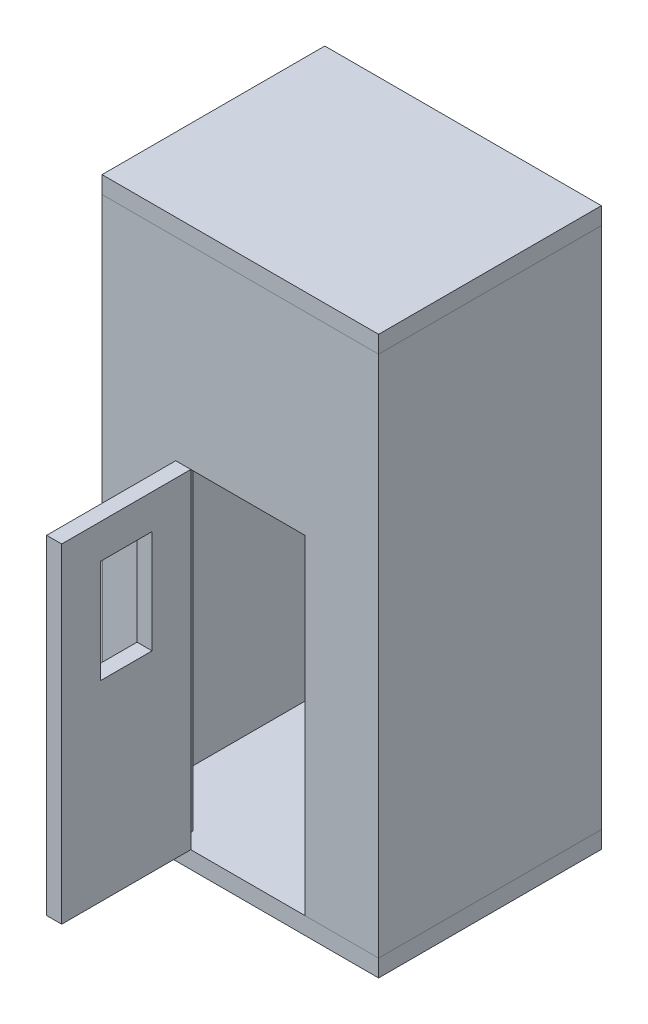
SolidWorks part; units mm, degrees
ref_plane "Front" through (0, 0, 0) normal (0, 0, 1) x (1, 0, 0)
ref_plane "Top" through (0, 0, 0) normal (0, 1, 0) x (1, 0, 0)
ref_plane "Right" through (0, 0, 0) normal (1, 0, 0) x (0, 0, -1)
sketch "Sketch1" plane through (0, 0, 0) normal (0, 1, 0) x (1, 0, 0)
  line L0 (-714.375, 555.625) -> (714.375, 555.625)
  line L1 (-815.975, -657.225) -> (815.975, -657.225)
  line L2 (-815.975, -657.225) -> (-815.975, 657.225)
  line L3 (-815.975, 657.225) -> (815.975, 657.225)
  line L4 (815.975, -657.225) -> (815.975, 657.225)
  line L5 (-815.975, -657.225) -> (815.975, 657.225) construction
  line L6 (-815.975, 657.225) -> (815.975, -657.225) construction
  line L7 (714.375, -555.625) -> (714.375, 555.625)
  line L8 (-714.375, -555.625) -> (714.375, -555.625)
  line L9 (-714.375, -555.625) -> (-714.375, 555.625)
  point P0 (0, 0)
  dimension "D1" = 1314.45
  dimension "D2" = 1631.95
  dimension "D3" = 101.6
extrude "Boss-Extrude1" add sketch "Sketch1" along normal blind 3086.1
sketch "Sketch2" plane through (0, 3086.1, 0) normal (0, 1, 0) x (1, 0, 0)
  line L4 (815.975, -657.225) -> (815.975, 657.225)
  line L5 (815.975, 657.225) -> (-815.975, 657.225)
  line L6 (-815.975, 657.225) -> (-815.975, -657.225)
  line L7 (-815.975, -657.225) -> (815.975, -657.225)
  line L8 (815.975, -657.225) -> (815.975, 657.225)
  line L9 (815.975, 657.225) -> (-815.975, 657.225)
  line L10 (-815.975, 657.225) -> (-815.975, -657.225)
  line L11 (-815.975, -657.225) -> (815.975, -657.225)
  dimension "D1" = 0
extrude "Boss-Extrude2" add sketch "Sketch2" along normal blind 101.6 separate body
sketch "Sketch3" plane through (0, 0, 657.225) normal (0, 0, 1) x (1, 0, 0)
  line L0 (-815.975, 0) -> (815.975, 0) construction
  line L1 (-381, 0) -> (381, 0)
  line L2 (-381, 0) -> (-381, 1943.1)
  line L3 (-381, 1943.1) -> (381, 1943.1)
  line L4 (381, 0) -> (381, 1943.1)
  line L5 (0, 1943.1) -> (0, 0) construction
  dimension "D1" = 1943.1
  dimension "D2" = 762
extrude "Cut-Extrude1" cut sketch "Sketch3" against normal up to next (101.6 mm away)
sketch "Sketch4" plane through (0, 0, 0) normal (0, -1, 0) x (1, 0, 0)
  line L1 (-815.975, -657.225) -> (815.975, -657.225)
  line L2 (-815.975, -657.225) -> (-815.975, 657.225)
  line L3 (-815.975, 657.225) -> (815.975, 657.225)
  line L4 (815.975, -657.225) -> (815.975, 657.225)
  line L5 (-815.975, -657.225) -> (815.975, 657.225) construction
  line L6 (-815.975, 657.225) -> (815.975, -657.225) construction
  point P0 (0, 0)
extrude "Boss-Extrude3" add sketch "Sketch4" along normal blind 101.6 separate body
sketch "Sketch5" plane through (0, 0, -555.625) normal (0, 0, 1) x (1, 0, 0)
  line L4 (-714.375, 0) -> (714.375, 0)
  line L5 (714.375, 0) -> (714.375, 3086.1)
  line L6 (714.375, 3086.1) -> (-714.375, 3086.1)
  line L7 (-714.375, 3086.1) -> (-714.375, 0)
  line L8 (-714.375, 0) -> (714.375, 0)
  line L9 (714.375, 0) -> (714.375, 3086.1)
  line L10 (714.375, 3086.1) -> (-714.375, 3086.1)
  line L11 (-714.375, 3086.1) -> (-714.375, 0)
  dimension "D1" = 0
extrude "Cut-Extrude2" cut sketch "Sketch5" against normal through all
sketch "Sketch6" plane through (0, 1943.1, 0) normal (0, -1, 0) x (1, 0, 0)
  line L0 (-381, 657.225) -> (-381, 1419.225)
  line L1 (-381, 1419.225) -> (-292.1, 1419.225)
  line L2 (-292.1, 1419.225) -> (-292.1, 657.225)
  line L3 (-292.1, 657.225) -> (-381, 657.225)
  line L4 (381, 657.225) -> (-381, 657.225) construction
  dimension "D1" = 762
  dimension "D2" = 88.9
  dimension "D3" = 90
extrude "Boss-Extrude4" add sketch "Sketch6" along normal up to surface (1943.1 mm away) separate body up to face at (0, 0, 0)
sketch "Sketch7" plane through (-381, 0, 0) normal (-1, 0, 0) x (0, 0, 1)
  line L0 (1419.225, 914.4) -> (1317.625, 914.4) construction
  line L1 (1419.225, 0) -> (1419.225, 1943.1) construction
  line L2 (657.225, 0) -> (1419.225, 0) construction
  circle A0 centre (1317.625, 914.4) radius 12.7
  dimension "D2" = 25.4
  dimension "D1" = 101.6
  dimension "D3" = 914.4
extrude "Boss-Extrude5" add sketch "Sketch7" along normal blind 50.8
sketch "Sketch8" plane through (-431.8, 0, 0) normal (-1, 0, 0) x (0, 0, 1)
  line L0 (1285.875, 914.4) -> (1349.375, 914.4)
  line L1 (1317.625, 927.1) -> (1317.625, 901.7) construction
  circle A0 centre (1317.625, 914.4) radius 12.7 construction
  circle A1 centre (1317.625, 914.4) radius 12.7 construction
  arc A2 (1349.375, 914.4) -> (1285.875, 914.4) centre (1317.625, 914.4) ccw
  point P9 (1317.625, 914.4)
  dimension "D1" = 31.75
revolve "Revolve1" add sketch "Sketch8" angle 360 about L0
sketch "Sketch9" plane through (-381, 0, 0) normal (-1, 0, 0) x (0, 0, 1)
  line L0 (1038.225, 1943.1) -> (1038.225, 1435.1) construction
  line L1 (1419.225, 1943.1) -> (657.225, 1943.1) construction
  line L3 (885.825, 1739.9) -> (1190.625, 1739.9)
  line L4 (885.825, 1739.9) -> (885.825, 1130.3)
  line L5 (885.825, 1130.3) -> (1190.625, 1130.3)
  line L6 (1190.625, 1739.9) -> (1190.625, 1130.3)
  line L7 (885.825, 1739.9) -> (1190.625, 1130.3) construction
  line L8 (885.825, 1130.3) -> (1190.625, 1739.9) construction
  dimension "D1" = 304.8
  dimension "D2" = 609.6
  dimension "D3" = 203.2
extrude "Cut-Extrude3" cut sketch "Sketch9" against normal up to surface (88.9 mm away) up to face at (-292.1, 971.55, 1038.225)
